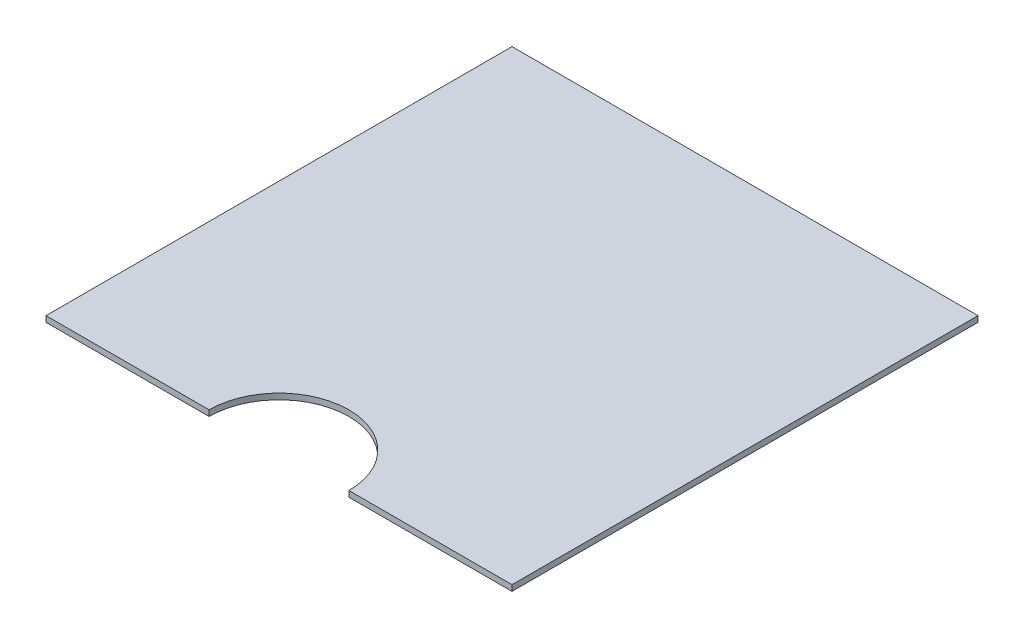
SolidWorks part; units mm, degrees
ref_plane "Front Plane" through (0, 0, 0) normal (0, 0, 1) x (1, 0, 0)
ref_plane "Top Plane" through (0, 0, 0) normal (0, 1, 0) x (1, 0, 0)
ref_plane "Right Plane" through (0, 0, 0) normal (1, 0, 0) x (0, 0, -1)
sketch "Sketch1" plane through (0, 0, 0) normal (0, 1, 0) x (1, 0, 0)
  line L1 (-200, -200) -> (200, -200)
  line L2 (-200, -200) -> (-200, 200)
  line L3 (-200, 200) -> (200, 200)
  line L4 (200, -200) -> (200, 200)
  line L5 (-200, -200) -> (200, 200) construction
  line L6 (-200, 200) -> (200, -200) construction
  point P0 (0, 0)
  dimension "D1" = 400
  dimension "D2" = 400
extrude "Boss-Extrude1" add sketch "Sketch1" along normal blind 5
sketch "Sketch2" plane through (0, 5, 0) normal (0, 1, 0) x (1, 0, 0)
  line L0 (-200, -200) -> (200, -200) construction
  line L1 (-60, -200) -> (60, -200)
  arc A0 (60, -200) -> (-60, -200) centre (0, -200) ccw
  dimension "D1" = 60
extrude "Cut-Extrude1" cut sketch "Sketch2" against normal blind 10
sketch "Sketch3" plane through (0, 5, 0) normal (0, 1, 0) x (1, 0, 0)
  line L0 (200, 200) -> (-200, 200) construction
  line L1 (-200, 200) -> (-200, -200) construction
  line L2 (0, -2.75) -> (0, 2.75) construction
  line L3 (-2.75, 0) -> (2.75, 0) construction
  circle A0 centre (-190, 190) radius 2
  circle A1 centre (190, 190) radius 2
  circle A2 centre (190, -190) radius 2
  circle A3 centre (-190, -190) radius 2
  dimension "D1" = 4
  dimension "D2" = 10
  dimension "D3" = 10
